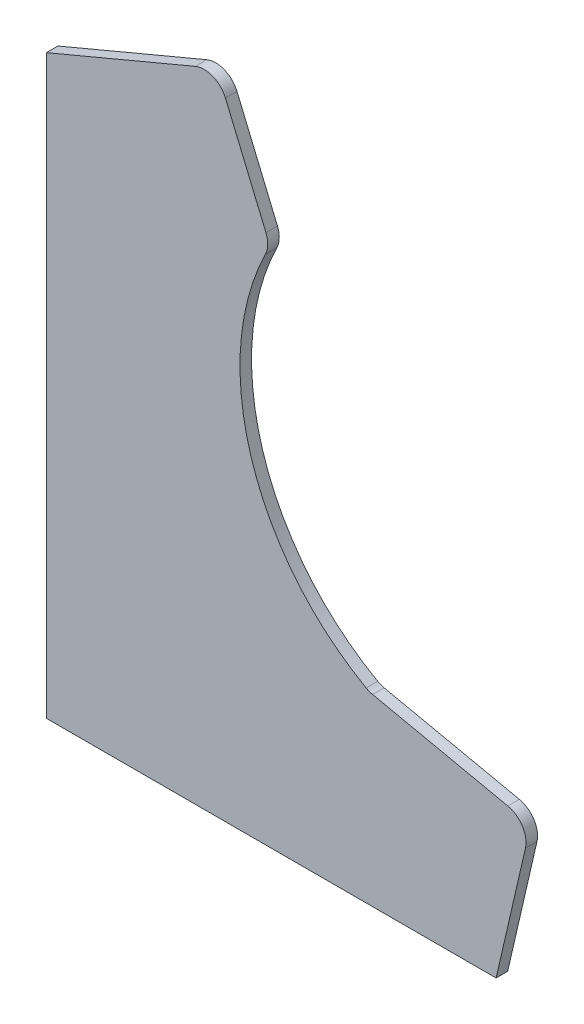
SolidWorks part; units mm, degrees
ref_plane "Plan de face" through (0, 0, 0) normal (0, 0, 1) x (1, 0, 0)
ref_plane "Plan de dessus" through (0, 0, 0) normal (0, 1, 0) x (1, 0, 0)
ref_plane "Plan de droite" through (0, 0, 0) normal (1, 0, 0) x (0, 0, -1)
sketch "Esquisse1" plane through (0, 0, 0) normal (0, 0, 1) x (1, 0, 0)
  line L0 (0, 0) -> (0, 500)
  line L1 (0, 0) -> (390, 0)
  line L2 (0, 500) -> (129.0626, 554.25)
  line L3 (155.25, 543.5626) -> (190.3729, 460.004)
  line L4 (390, 0) -> (415.4316, 110.2037)
  line L5 (400.1344, 134.2569) -> (282.8933, 159.38)
  arc A0 (189.8854, 443.4335) -> (277.2694, 161.5098) centre (382.69, 348.69) ccw
  arc A1 (155.25, 543.5626) -> (129.0626, 554.25) centre (136.8126, 535.8126) ccw
  arc A2 (400.1344, 134.2569) -> (415.4316, 110.2037) centre (395.9438, 114.7009) cw
  arc A3 (189.8854, 443.4335) -> (190.3729, 460.004) centre (171.9355, 452.254) ccw
  arc A4 (282.8933, 159.38) -> (277.2694, 161.5098) centre (287.0839, 178.9361) cw
  point P12 (147.5, 562)
  point P15 (420, 130)
  point P18 (193.9979, 451.38)
  dimension "D13" = 20
  dimension "D14" = 20
  dimension "D15" = 20
  dimension "D7" = 20
  dimension "D1" = 390
  dimension "D2" = 500
  dimension "D3" = 62
  dimension "D4" = 147.5
  dimension "D5" = 110.62
  dimension "D6" = 420
  dimension "D10" = 382.69
  dimension "D11" = 348.69
extrude "Boss.-Extru.1" add sketch "Esquisse1" along normal blind 10
